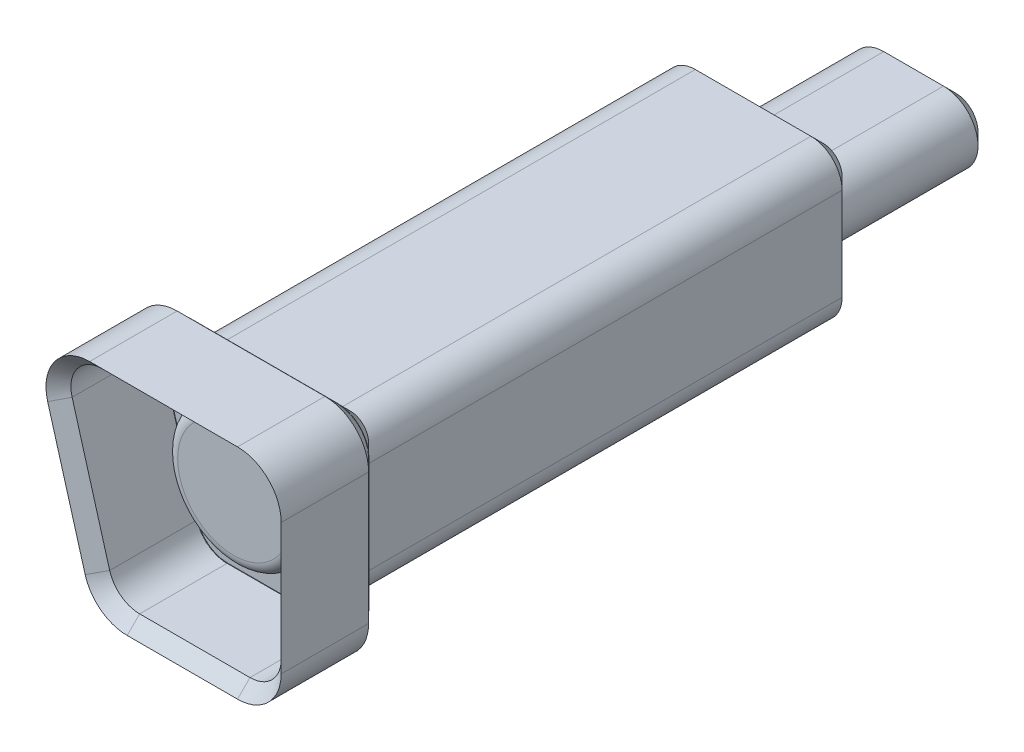
SolidWorks part; units mm, degrees
ref_plane "Front Plane" through (0, 0, 0) normal (0, 0, 1) x (1, 0, 0)
ref_plane "Top Plane" through (0, 0, 0) normal (0, 1, 0) x (1, 0, 0)
ref_plane "Right Plane" through (0, 0, 0) normal (1, 0, 0) x (0, 0, -1)
sketch "Sketch1" plane through (0, 0, 0) normal (0, 0, 1) x (1, 0, 0)
  line L0 (-12.594, 16.7008) -> (88.9795, 16.7008)
  line L1 (88.9795, 16.7008) -> (88.9795, -72.2787)
  line L2 (88.9795, -72.2787) -> (12.8678, -72.2787)
  line L3 (12.8678, -72.2787) -> (-12.594, 16.7008)
extrude "Boss-Extrude1" add sketch "Sketch1" along normal blind 50.8
fillet "Fillet1" radius 17.78 4 edges at (88.9795, -72.2787, 25.4) (88.9795, 16.7008, 25.4) (12.8678, -72.2787, 25.4) (-12.594, 16.7008, 25.4)
shell "Shell2" thickness 5.08 removed face at (45.0312, -28.837, 50.8)
sketch "Sketch2" plane through (0, 0, 5.08) normal (0, 0, 1) x (1, 0, 0)
  line L0 (78.329, 3.9302) -> (1.6012, 3.9302)
  line L1 (1.6012, 3.9302) -> (20.1563, -59.2574)
  line L2 (20.1563, -59.2574) -> (78.329, -59.2574)
  line L3 (78.329, -59.2574) -> (78.329, 3.9302)
extrude "Boss-Extrude3" add sketch "Sketch2" against normal blind 203.2 contours L3 L0 L1 L2
fillet "Fillet2" radius 12.7 4 edges at (20.1563, -59.2574, -99.06) (1.6012, 3.9302, -99.06) (78.329, -59.2574, -99.06) (78.329, 3.9302, -99.06)
sketch "Sketch3" plane through (0, 0, 0) normal (0, 0, -1) x (-1, 0, 0)
  circle A0 centre (-42.8099, -26.4195) radius 27.8701
extrude "Boss-Extrude4" add sketch "Sketch3" against normal blind 19.05
fillet "Fillet4" radius 5.08 1 edges at (14.9398, -26.4195, 19.05)
sketch "Sketch7" plane through (0, 0, -198.12) normal (0, 0, -1) x (-1, 0, 0)
  line L0 (-56.1381, -28.9173) -> (-31.8159, -28.9173) construction
  line L1 (-56.1381, -14.8756) -> (-31.8159, -14.8756)
  line L2 (-56.1381, -42.959) -> (-31.8159, -42.959)
  arc A0 (-56.1381, -14.8756) -> (-56.1381, -42.959) centre (-56.1381, -28.9173) ccw
  arc A1 (-31.8159, -42.959) -> (-31.8159, -14.8756) centre (-31.8159, -28.9173) ccw
  point P2 (-43.977, -28.9173)
extrude "Boss-Extrude5" add sketch "Sketch7" along normal blind 63.5
chamfer "Chamfer2" distance 10 angle 45 8 edges at (80.1797, -63.479, 50.8) (83.8995, -27.789, 50.8) (80.1797, 7.901, 50.8) (41.0935, 11.6208, 50.8) (0.8468, 6.5666, 50.8) (6.4206, -31.2829, 50.8) (18.6278, -64.6393, 50.8) (48.7365, -67.1987, 50.8)
chamfer "Chamfer3" distance 4.92 angle 45 4 edges at (43.977, -14.8756, -261.62) (17.7742, -28.9173, -261.62) (43.977, -42.959, -261.62) (70.1798, -28.9173, -261.62)
chamfer "Chamfer4" distance 4.92 angle 45 8 edges at (74.6092, -55.5377, -198.12) (47.6461, -59.2574, -198.12) (78.329, -27.6636, -198.12) (22.0525, -56.7244, -198.12) (74.6092, 0.2104, -198.12) (11.9295, -31.2419, -198.12) (42.0979, 3.9302, -198.12) (8.3999, -1.1591, -198.12)
chamfer "Chamfer5" distance 10.254 angle 45 8 edges at (48.7365, -72.2787, 0) (83.7718, -67.0711, 0) (15.5695, -68.6955, 0) (88.9795, -27.789, 0) (1.5366, -32.6805, 0) (83.7718, 11.4931, 0) (-3.2094, 9.6249, 0) (41.0935, 16.7008, 0)
